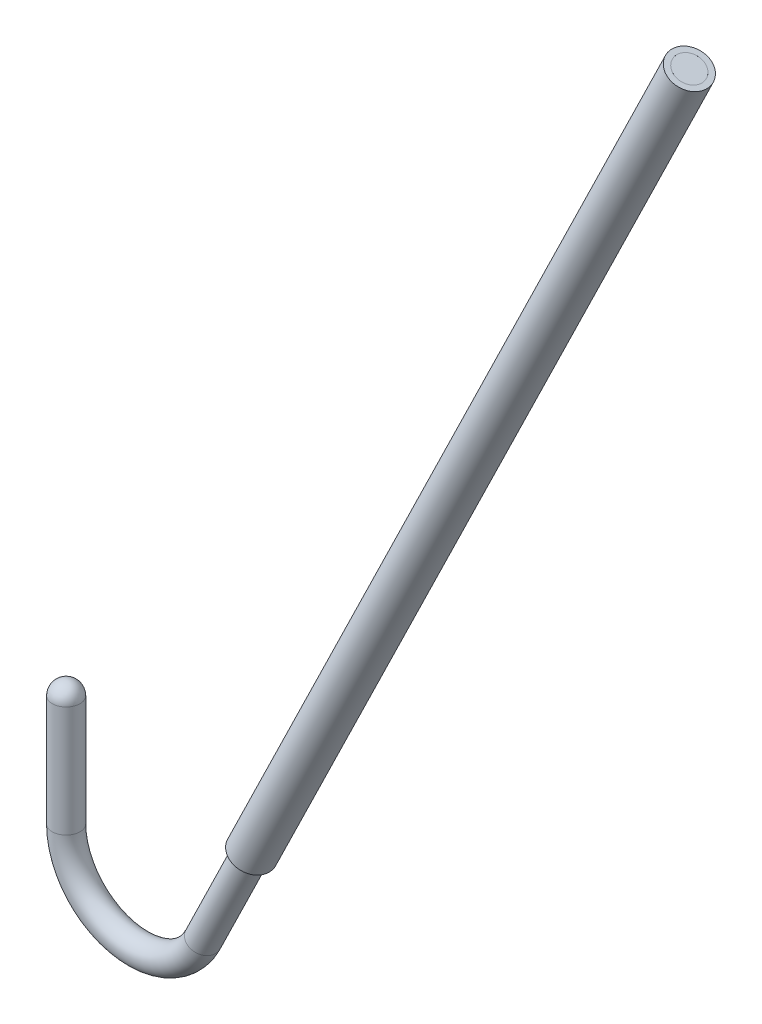
SolidWorks part; units mm, degrees
ref_plane "Front Plane" through (0, 0, 0) normal (0, 0, 1) x (1, 0, 0)
ref_plane "Top Plane" through (0, 0, 0) normal (0, 1, 0) x (1, 0, 0)
ref_plane "Right Plane" through (0, 0, 0) normal (1, 0, 0) x (0, 0, -1)
sketch "Sketch1" plane through (0, 0, 0) normal (0, 1, 0) x (1, 0, 0)
  circle A0 centre (0, 0) radius 0.25
  dimension "D1" = 0.5
sketch "Sketch2" plane through (0, 0, 0) normal (0, 0, 1) x (1, 0, 0)
  line L0 (0, 0) -> (0, -2)
  line L1 (2.4684, -2.5699) -> (11.2359, 15.406)
  arc A0 (0, -2) -> (2.4684, -2.5699) centre (1.3, -2) ccw
  dimension "D2" = 1.3
  dimension "D1" = 2
  dimension "D3" = 20
  dimension "D4" = 26
sweep "Sweep1" add profiles "Sketch1" path "Sketch2"
sketch "Sketch3" plane through (0, 0, 0) normal (1, 0, 0) x (0, 0, -1)
  line L0 (0, -0.25) -> (0, 0.25)
  line L7 (0.25, 0) -> (-0.25, 0) construction
  arc A0 (0, 0.25) -> (0, -0.25) centre (0, 0) ccw
  point P7 (-0.25, 0)
  dimension "D1" = 0.25
revolve "Revolve1" add sketch "Sketch3" angle 360 about L0
sketch "Sketch4" plane through (8.2292, 16.8724, 0) normal (0.4384, 0.8988, 0) x (0.8988, -0.4384, 0)
  circle A0 centre (3.3452, 0) radius 0.35
  circle A1 centre (3.3452, 0) radius 0.25
  circle A2 centre (3.3452, 0) radius 0.25
  dimension "D1" = 0
  dimension "D2" = 0.1
extrude "Boss-Extrude1" add sketch "Sketch4" against normal blind 18 separate body
ref_plane "Plane1" through (2.7441, -1.1087, -0.3572) normal (-0.9205, 0.3719, 0.1198) x (0.3746, 0.9272, 0)
ref_axis "Axis1" through (0, 0, 0) along (0, -1, 0)
